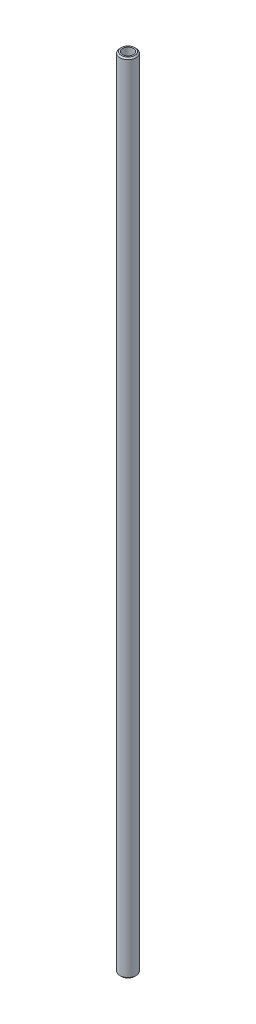
SolidWorks part; units mm, degrees
ref_plane "Plan de face" through (0, 0, 0) normal (0, 0, 1) x (1, 0, 0)
ref_plane "Plan de dessus" through (0, 0, 0) normal (0, 1, 0) x (1, 0, 0)
ref_plane "Plan de droite" through (0, 0, 0) normal (1, 0, 0) x (0, 0, -1)
sketch "Esquisse2" plane through (0, 0, 0) normal (0, 1, 0) x (1, 0, 0)
  line L0 (2755.2141, -504.598) -> (2772.6964, -531.9955) construction
  circle A0 centre (2763.9553, -518.2967) radius 3
  circle A1 centre (2763.9553, -518.2967) radius 2
  dimension "D1" = 6
  dimension "D2" = 4
extrude "Boss.-Extru.1" add sketch "Esquisse2" along normal blind 295
chamfer "Chanfrein1" distance 0.5 angle 45 2 edges at (2763.9553, 295, 521.2967) (2763.9553, 0, 521.2967)
